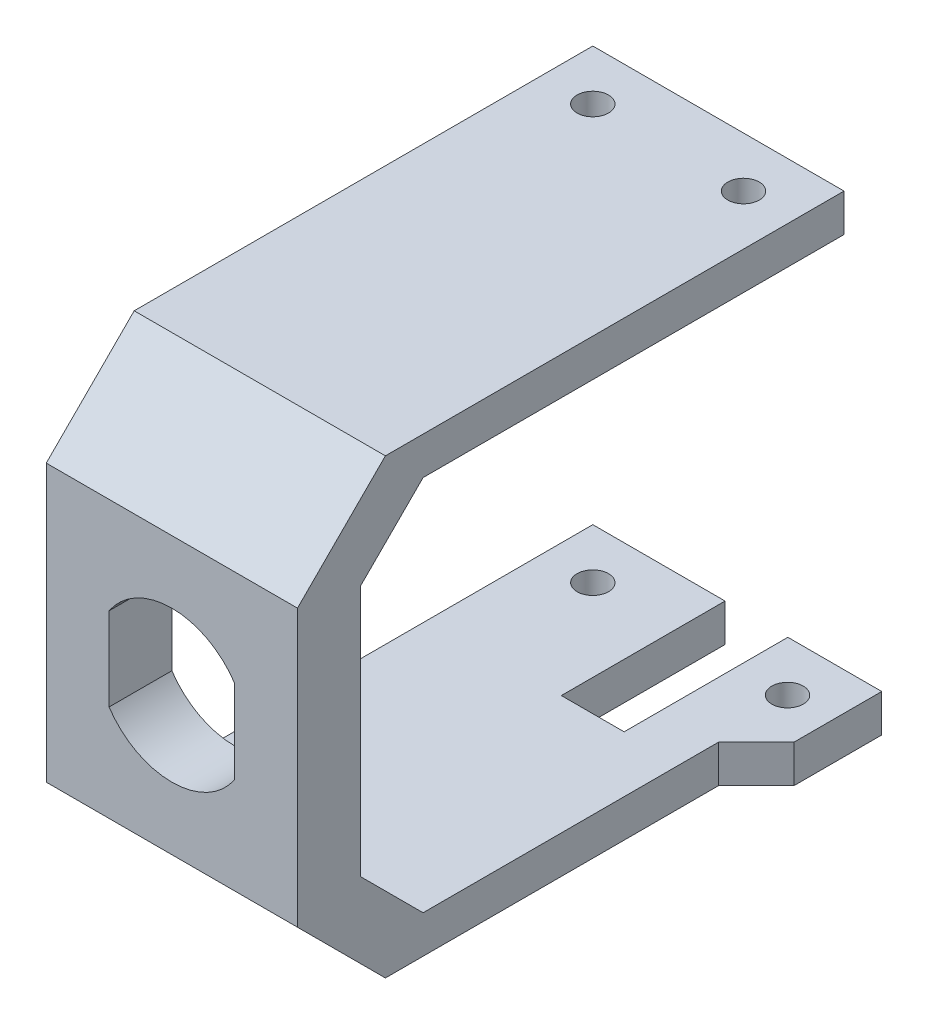
SolidWorks part; units mm, degrees
ref_plane "前视基准面" through (0, 0, 0) normal (0, 0, 1) x (1, 0, 0)
ref_plane "上视基准面" through (0, 0, 0) normal (0, 1, 0) x (1, 0, 0)
ref_plane "右视基准面" through (0, 0, 0) normal (1, 0, 0) x (0, 0, -1)
other "Configuration Table"
ref_plane "基准面1" through (0, 0, 45) normal (0, 0, 1) x (1, 0, 0)
sketch "草图2" plane through (0, 0, 38.51) normal (0, 0, 1) x (1, 0, 0)
  line L0 (81.9336, 6) -> (118.8757, 6) construction
  line L1 (89.3, 15) -> (109.3, 15)
  line L2 (104.3, -3.3166) -> (104.3, 3.3166)
  line L3 (94.3, 3.3166) -> (94.3, -3.3166)
  line L4 (104.3, -3.3166) -> (104.3, 3.3166)
  line L5 (94.3, 3.3166) -> (94.3, -3.3166)
  line L6 (89.3, 15) -> (89.3, -15)
  line L7 (89.3, -15) -> (109.3, -15)
  line L8 (109.3, 15) -> (109.3, -15)
  line L9 (89.3, 15) -> (109.3, -15) construction
  line L10 (89.3, -15) -> (109.3, 15) construction
  line L11 (79.3, 15) -> (107.3, 15) construction
  arc A2 (94.3, -3.3166) -> (104.3, -3.3166) centre (99.3, 0) ccw
  arc A3 (104.3, 3.3166) -> (94.3, 3.3166) centre (99.3, 0) ccw
  arc A4 (94.3, -3.3166) -> (104.3, -3.3166) centre (99.3, 0) ccw
  arc A5 (104.3, 3.3166) -> (94.3, 3.3166) centre (99.3, 0) ccw
  dimension "D2" = 5
  dimension "D1" = 0
extrude "凸台-拉伸1" add sketch "草图2" along normal blind 5
sketch "草图5" plane through (0, 0, 43.51) normal (0, 0, 1) x (1, 0, 0)
  line L1 (89.3, -15) -> (109.3, -15)
  line L2 (89.3, -15) -> (89.3, -18)
  line L3 (89.3, -18) -> (109.3, -18)
  line L4 (109.3, -15) -> (109.3, -18)
  line L5 (109.3, -15) -> (109.3, 15) construction
  line L6 (89.3, 15) -> (109.3, 15)
  line L7 (89.3, 15) -> (89.3, 18)
  line L8 (89.3, 18) -> (109.3, 18)
  line L9 (109.3, 15) -> (109.3, 18)
  line L10 (109.3, 15) -> (89.3, 15) construction
  line M2 (109.3, 15) -> (89.3, 15)
  line M4 (89.3, -15) -> (109.3, -15)
  dimension "D1" = 3
  dimension "D2" = 3
extrude "凸台-拉伸3" add sketch "草图5" against normal up to surface (43.51 mm away) contours L9 L8 L7 M2 | L4 L2 L3 M4 region at (99.3, -16.5, 43.51) region at (99.3, 16.5, 43.51) up to plane "前视基准面"
sketch "草图6" plane through (0, -18, 0) normal (0, -1, 0) x (1, 0, 0)
  line L0 (109.3, 0) -> (89.3, 0) construction
  line L1 (99.8297, 1.0966) -> (104.8297, 1.0966)
  line L2 (99.8297, 1.0966) -> (99.8297, 0)
  line L3 (99.8297, 0) -> (104.8297, 0)
  line L4 (104.8297, 1.0966) -> (104.8297, 9.6924)
  line L5 (104.8297, 9.6924) -> (99.8297, 9.6924)
  line L6 (99.8297, 9.6924) -> (99.8297, 1.0966)
  line L7 (99.8297, 1.0966) -> (104.8297, 1.0966)
  line L8 (104.8297, 1.0966) -> (104.8297, 9.6924)
  line L10 (99.8297, 9.6924) -> (99.8297, 1.0966)
  line L11 (99.8297, 1.0966) -> (104.8297, 1.0966)
  line L12 (104.8297, 9.5819) -> (104.8297, 14.535)
  line L13 (99.8297, 9.5819) -> (104.8297, 9.5819)
  line L14 (99.8297, 14.535) -> (99.8297, 9.5819)
  line L15 (104.8297, 14.535) -> (99.8297, 14.535)
  line L16 (104.8297, 9.5819) -> (104.8297, 14.535)
  line L18 (99.8297, 14.535) -> (99.8297, 9.5819)
  line L19 (104.8297, 14.535) -> (99.8297, 14.535)
  line L20 (104.8297, 1.0966) -> (104.8297, 0)
  line L21 (99.8297, 13.035) -> (104.8297, 13.035)
  line M5 (89.3, 0) -> (109.3, 0)
  dimension "D3" = 1.5
  dimension "D1" = 0
  dimension "D2" = 0
extrude "切除-拉伸2" cut sketch "草图6" against normal up to next contours L21 L18 L10 L1 L8 L16 | L20 L1 L2 M5 region at (102.3297, -18, 5.3392) region at (102.3297, -18, 0.5483) region at (102.3297, -18, 9.6371) region at (102.3297, -18, 11.3637)
sketch "草图7" plane through (0, -18, 0) normal (0, -1, 0) x (1, 0, 0)
  line L0 (109.3, 10) -> (112.3027, 6.9973)
  line L1 (109.3, 0) -> (109.3, 43.51) construction
  line L2 (112.3027, 6.9973) -> (112.3027, 0)
  line L3 (112.3027, 0) -> (109.3, 0)
  line L4 (109.3, 10) -> (109.3, 0)
  dimension "D1" = 3.0027
  dimension "D2" = 45
  dimension "D3" = 10
extrude "凸台-拉伸4" add sketch "草图7" against normal up to surface (3 mm away)
sketch "草图8" plane through (0, -18, 0) normal (0, -1, 0) x (1, 0, 0)
  line L1 (99.8297, 0) -> (89.3, 0) construction
  line L2 (89.3, 0) -> (89.3, 43.51) construction
  line L3 (112.3027, 0) -> (104.8297, 0) construction
  line L4 (112.3027, 0) -> (112.3027, 6.9973) construction
  circle A0 centre (93.3, 4) radius 1.25
  circle A1 centre (108.8027, 4) radius 1.25
  dimension "D1" = 2.5
  dimension "D5" = 3.5
  dimension "D6" = 2.5
  dimension "D2" = 4
  dimension "D3" = 4
  dimension "D4" = 4
extrude "切除-拉伸3" cut sketch "草图8" against normal up to next
sketch "草图9" plane through (0, 18, 0) normal (0, 1, 0) x (1, 0, 0)
  line L0 (109.3, 0) -> (109.3, -43.51) construction
  line L1 (109.3, 0) -> (89.3, 0) construction
  line L2 (89.3, 0) -> (89.3, -43.51) construction
  circle A0 centre (105.3, -4) radius 1.25
  circle A1 centre (93.3, -4) radius 1.25
  dimension "D1" = 2.5
  dimension "D2" = 2.5
  dimension "D3" = 4
  dimension "D4" = 4
  dimension "D5" = 4
extrude "切除-拉伸4" cut sketch "草图9" against normal up to next
chamfer "倒角2" distance 5 angle 45 2 edges at (99.3, 15, 38.51) (99.3, -15, 38.51)
chamfer "倒角3" distance 7 angle 45 2 edges at (99.3, 18, 43.51) (99.3, -18, 43.51)
